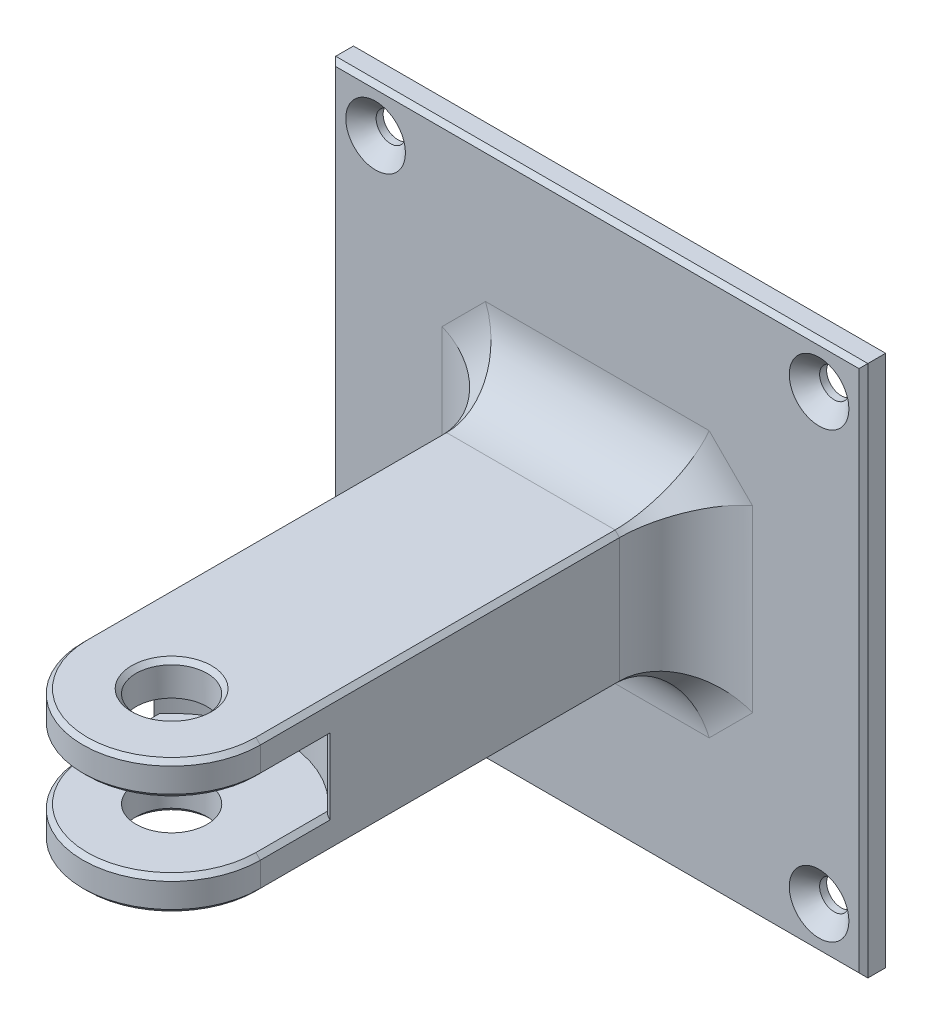
SolidWorks part; units mm, degrees
material "6061 Alloy"
ref_plane "Front Plane" through (0, 0, 0) normal (0, 0, 1) x (1, 0, 0)
ref_plane "Top Plane" through (0, 0, 0) normal (0, 1, 0) x (1, 0, 0)
ref_plane "Right Plane" through (0, 0, 0) normal (1, 0, 0) x (0, 0, -1)
sketch "Sketch1" plane through (0, 0, 0) normal (0, 0, 1) x (1, 0, 0)
  line L1 (60, -60) -> (-60, -60)
  line L2 (60, -60) -> (60, 60)
  line L3 (60, 60) -> (-60, 60)
  line L4 (-60, -60) -> (-60, 60)
  line L5 (60, -60) -> (-60, 60) construction
  line L6 (60, 60) -> (-60, -60) construction
  point P0 (0, 0)
  dimension "D1" = 120
extrude "Boss-Extrude1" add sketch "Sketch1" along normal blind 5
sketch "Sketch2" plane through (0, 0, 5) normal (0, 0, 1) x (1, 0, 0)
  line L1 (50, -50) -> (-50, -50) construction
  line L2 (50, -50) -> (50, 50) construction
  line L3 (50, 50) -> (-50, 50) construction
  line L4 (-50, -50) -> (-50, 50) construction
  line L5 (50, -50) -> (-50, 50) construction
  line L6 (50, 50) -> (-50, -50) construction
  point P0 (0, 0)
  point P7 (-50, 50)
  point P8 (50, 50)
  point P9 (50, -50)
  point P10 (-50, -50)
  dimension "D1" = 100
hole_wizard "CSK for M6 SFHCS1" positions "Sketch3" profile "Sketch4" countersink size "M6" standard "ANSI Metric" end condition through all
sketch "Sketch3" plane through (0, 0, 5) normal (0, 0, 1) x (1, 0, 0)
  point P0 (-50, 50)
  point P3 (50, 50)
  point P6 (50, -50)
  point P9 (-50, -50)
sketch "Sketch4" plane through (-50, 50, 5) normal (1, 0, 0) x (0, -1, 0)
  line L0 (0, 0) -> (0, 5)
  line L1 (0, 5) -> (3.3, 5)
  line L2 (3.3, 5) -> (3.3, 3.42)
  line L3 (3.3, 3.42) -> (6.72, 0)
  line L5 (6.72, 0) -> (0, 0)
  line L6 (-3.3, 3.42) -> (-6.72, 0) construction
  line L11 (0, -6.35) -> (0, 107.95) construction
  dimension "Thru Hole Dia." = 6.6
  dimension "Thru Hole Depth" = 5
  dimension "Near C'Sink Dia." = 13.44
  dimension "Near C'Sink Angle" = 90
sketch "Sketch5" plane through (0, 0, 0) normal (1, 0, 0) x (0, 0, -1)
  line L0 (-5, -60) -> (-5, 60) construction
  line L1 (-5, 15) -> (-101, 15)
  line L2 (-5, 15) -> (-5, -15)
  line L3 (-5, -15) -> (-101, -15)
  line L4 (-101, 15) -> (-101, -15)
  line L5 (-1000, 0) -> (49000, 0) construction
  line L6 (0, -60) -> (0, 60) construction
  dimension "D1" = 30
  dimension "D2" = 101
extrude "Boss-Extrude2" add sketch "Sketch5" along normal mid plane 40
sketch "Sketch6" plane through (0, 0, 0) normal (0, 1, 0) x (1, 0, 0)
  line L0 (20, -101) -> (-20, -101) construction
  circle A0 centre (0, -101) radius 20
extrude "Boss-Extrude3" add sketch "Sketch6" along normal mid plane 30
sketch "Sketch7" plane through (0, 0, 0) normal (0, 1, 0) x (1, 0, 0)
  circle A0 centre (0, -101) radius 25
  dimension "D1" = 50
extrude "Cut-Extrude2" cut sketch "Sketch7" against normal mid plane 15
sketch "Sketch8" plane through (0, 15, 0) normal (0, 1, 0) x (1, 0, 0)
  circle A0 centre (0, -101) radius 8
  dimension "D1" = 16
extrude "Cut-Extrude3" cut sketch "Sketch8" against normal through all
chamfer "Chamfer1" distance 1 angle 45 16 edges at (-20, -7.5, 93.5) (0, -7.5, 121) (20, -7.5, 93.5) (-20, 7.5, 93.5) (0, 7.5, 121) (20, 7.5, 93.5) (-20, 15, 53) (20, 15, 53) (0, 15, 121) (0, 15, 109) (0, -15, 109) (-20, -15, 53) (20, -15, 53) (0, -15, 121) (20, 0, 86) (-20, 0, 86)
fillet "Fillet1" radius 15 8 edges at (-20, 0, 5) (0, 15, 5) (-19.5, 14.5, 5) (19.5, 14.5, 5) (20, 0, 5) (19.5, -14.5, 5) (0, -15, 5) (-19.5, -14.5, 5)
chamfer "Chamfer2" distance 1 angle 45 4 edges at (0, -60, 5) (60, 0, 5) (0, 60, 5) (-60, 0, 5)
